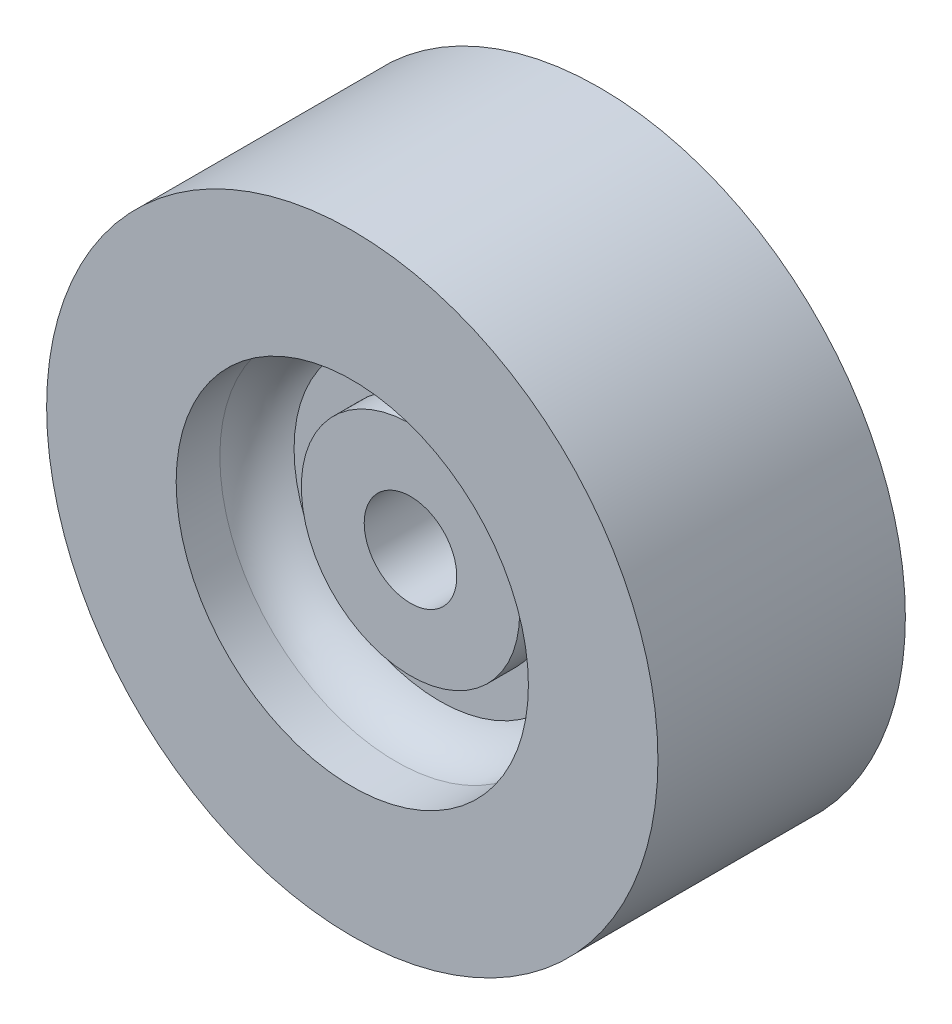
SolidWorks part; units mm, degrees
ref_plane "Front Plane" through (0, 0, 0) normal (0, 0, 1) x (1, 0, 0)
ref_plane "Top Plane" through (0, 0, 0) normal (0, 1, 0) x (1, 0, 0)
ref_plane "Right Plane" through (0, 0, 0) normal (1, 0, 0) x (0, 0, -1)
sketch "Sketch1" plane through (0, 0, 0) normal (1, 0, 0) x (0, 0, -1)
  line L0 (-0.0107, 12.1) -> (-0.0107, 14.8643)
  line L1 (-0.0107, 25.1) -> (24.9893, 25.1)
  line L2 (-0.0107, 22.1) -> (2.9893, 22.1)
  line L3 (2.9893, 10) -> (2.9893, 7.5)
  line L4 (2.9893, 7.5) -> (0.9893, 7.5)
  line L5 (0.9893, 7.5) -> (0.9893, 0)
  line L6 (-13.2759, 0) -> (14.215, 0) construction
  line L7 (-0.0107, 22.1) -> (-0.0107, 25.1)
  line L8 (24.9893, 25.1) -> (24.9893, 22.1)
  line L9 (24.9893, 22.1) -> (4.0868, 22.1)
  line L10 (0.9893, 14.8643) -> (0.9893, 12.992)
  line L11 (4.0868, 10) -> (8.0868, 10)
  line L12 (8.0868, 10) -> (8.0868, 0)
  line L13 (8.0868, 0) -> (0.9893, 0)
  arc A0 (-0.0107, 12.1) -> (2.9893, 10) centre (-0.3983, 8.3534) cw
  arc A1 (4.0868, 22.1) -> (0.9893, 14.8643) centre (9.2266, 15.6189) ccw
  arc A2 (0.9893, 12.992) -> (4.0868, 10) centre (-0.1123, 8.7522) cw
  spline S0 degree 3 poles (2.9893, 22.1) (1.2339, 21.0874) (0.2751, 20.019) (-0.0107, 14.8643) knots 0 0 0 0 1 1 1 1
  point P6 (3, 12)
  dimension "D5" = 2.2559
  dimension "D2" = 25
  dimension "D3" = 3
  dimension "D4" = 3
  dimension "D6" = 2
  dimension "D7" = 2.5
  dimension "D8" = 2
  dimension "D9" = 13
  dimension "D10" = 1
  dimension "D11" = 1
  dimension "D12" = 4
revolve "Revolve1" add sketch "Sketch1" angle 360 about L6
sketch "Sketch2" plane through (0, 0, 0.0107) normal (0, 0, 1) x (1, 0, 0)
  line L0 (0, 22.1) -> (0, 0) construction
  line L1 (-10, 19.7081) -> (-2.1298, 16.0027)
  line L2 (2.1298, 16.0027) -> (10, 19.7081)
  line L3 (15.6534, 15.6007) -> (14.5614, 6.9707)
  line L4 (15.8777, 2.9195) -> (21.8337, -3.4204)
  line L5 (19.6743, -10.0664) -> (11.1292, -11.6946)
  line L6 (7.6831, -14.1984) -> (3.494, -21.8221)
  line L7 (-3.494, -21.8221) -> (-7.6831, -14.1984)
  line L8 (-11.1292, -11.6946) -> (-19.6743, -10.0664)
  line L9 (-21.8337, -3.4204) -> (-15.8777, 2.9195)
  line L10 (-14.5614, 6.9707) -> (-15.6534, 15.6007)
  circle A0 centre (0, 0) radius 22.1 construction
  circle A1 centre (0, 0) radius 22.1 construction
  arc A2 (-2.1298, 16.0027) -> (2.1298, 16.0027) centre (0, 20.5264) ccw
  arc A3 (10, 19.7081) -> (-10, 19.7081) centre (0, 0) ccw
  arc A4 (14.5614, 6.9707) -> (15.8777, 2.9195) centre (19.5218, 6.343) ccw
  arc A5 (21.8337, -3.4204) -> (15.6534, 15.6007) centre (0, 0) ccw
  arc A6 (11.1292, -11.6946) -> (7.6831, -14.1984) centre (12.0651, -16.6062) ccw
  arc A7 (3.494, -21.8221) -> (19.6743, -10.0664) centre (0, 0) ccw
  arc A8 (-7.6831, -14.1984) -> (-11.1292, -11.6946) centre (-12.0651, -16.6062) ccw
  arc A9 (-19.6743, -10.0664) -> (-3.494, -21.8221) centre (0, 0) ccw
  arc A10 (-15.8777, 2.9195) -> (-14.5614, 6.9707) centre (-19.5218, 6.343) ccw
  arc A11 (-15.6534, 15.6007) -> (-21.8337, -3.4204) centre (0, 0) ccw
  point P12 (0, 15)
  point P35 (0, 0)
  dimension "D3" = 5
  dimension "D1" = 10
  dimension "D2" = 15
  dimension "D4" = 5
extrude "Cut-Extrude1" cut sketch "Sketch2" against normal blind 10
sketch "Sketch3" plane through (0, 0, -8.0868) normal (0, 0, -1) x (-1, 0, 0)
  circle A0 centre (0, 0) radius 6
  dimension "D1" = 12
extrude "Boss-Extrude1" add sketch "Sketch3" along normal blind 25
sketch "Sketch4" plane through (0, 0, -33.0868) normal (0, 0, -1) x (-1, 0, 0)
  line L0 (-2.5475, 2.4) -> (2.5475, 2.4)
  line L1 (-3.5, 0) -> (3.5, 0) construction
  line L2 (-2.5475, -2.4) -> (2.5475, -2.4)
  arc A0 (-2.5475, 2.4) -> (-2.5475, -2.4) centre (0, 0) ccw
  arc A1 (2.5475, -2.4) -> (2.5475, 2.4) centre (0, 0) ccw
  dimension "D1" = 7
  dimension "D2" = 2.4
extrude "Cut-Extrude2" cut sketch "Sketch4" against normal blind 12
sketch "Sketch5" plane through (0, 0, 0) normal (1, 0, 0) x (0, 0, -1)
  line L1 (-0.0107, 25.1) -> (-0.0107, -25.1) construction
  line L2 (24.9893, -25.1) -> (24.9893, 25.1) construction
  line L3 (12.4893, 21.6) -> (12.4893, 27) construction
  line L4 (0, 0) -> (33.0868, 0) construction
  line L5 (33.0868, -2.4) -> (33.0868, 2.4) construction
  line L6 (-0.0107, 14.6) -> (-0.0107, 24.9185)
  line L7 (-0.0107, 24.9185) -> (24.9893, 25.1)
  line L8 (24.9893, 25.1) -> (24.9893, 14.6)
  arc A0 (12.4893, 21.6) -> (0.6779, 20.7166) centre (11.5988, -45.8941) ccw
  arc A1 (-0.1468, 19.8936) -> (-0.0107, 14.6) centre (13.6641, 17.6) ccw
  arc A2 (-0.1468, 19.8936) -> (0.6779, 20.7166) centre (0.8397, 19.7297) cw
  arc A3 (25.1253, 19.8936) -> (24.9893, 14.6) centre (11.3145, 17.6) cw
  arc A4 (25.1253, 19.8936) -> (24.3006, 20.7166) centre (24.1389, 19.7297) ccw
  arc A5 (12.4893, 21.6) -> (24.3006, 20.7166) centre (13.3798, -45.8941) cw
  point P6 (12.4893, 21.6)
  point P7 (-0.0107, 20.6)
  point P8 (12.4893, 31.1)
  point P21 (-0.0107, 20.6)
  dimension "D3" = 67.5
  dimension "D4" = 14
  dimension "D5" = 1
  dimension "D2" = 6
  dimension "D6" = 21.6
revolve "Revolve2" add sketch "Sketch5" angle 360 about L4 rebuild error yes other way angle 360
sketch "Croquis2" plane through (0, 0, -24.9893) normal (0, 0, -1) x (-1, 0, 0)
  circle A0 centre (0, 0) radius 22.1
  circle A1 centre (0, 0) radius 25.1
extrude "Cortar-Extruir2" cut sketch "Croquis2" against normal blind 10
sketch "Croquis3" plane through (0, 0, -33.0868) normal (0, 0, -1) x (-1, 0, 0)
  circle A1 centre (0, 0) radius 6
  circle A2 centre (0, 0) radius 6
  dimension "D1" = 0
extrude "Cortar-Extruir3" cut sketch "Croquis3" against normal blind 26
sketch "Croquis5" plane through (0, 0, -8.0868) normal (0, 0, -1) x (-1, 0, 0)
  circle A1 centre (0, 0) radius 10
  circle A2 centre (0, 0) radius 10
  dimension "D1" = 0
extrude "Cortar-Extruir4" cut sketch "Croquis5" against normal up to surface (1 mm away) up to face at (-6, 0, -7.0868)
sketch "Croquis6" plane through (0, 0, -7.0868) normal (0, 0, -1) x (-1, 0, 0)
  circle A0 centre (0, 0) radius 3.1817
extrude "Cortar-Extruir5" cut sketch "Croquis6" against normal blind 26
sketch "Croquis7" plane through (0, 0, 0.0107) normal (0, 0, 1) x (1, 0, 0)
  circle A0 centre (0, 0) radius 20
  circle A1 centre (0, 0) radius 25.1
  dimension "D1" = 40
extrude "Cortar-Extruir6" cut sketch "Croquis7" against normal blind 100
sketch "Croquis8" plane through (0, 0, 0.0107) normal (0, 0, 1) x (1, 0, 0)
  circle A0 centre (0, 0) radius 21
  circle A1 centre (0, 0) radius 14
  dimension "D1" = 28
  dimension "42" = 42
extrude "Saliente-Extruir1" add sketch "Croquis8" against normal blind 14
sketch "Croquis9" plane through (0, 0, 0.0107) normal (0, 0, 1) x (1, 0, 0)
  circle A0 centre (0, 0) radius 12.1
  circle A1 centre (0, 0) radius 21
  circle A2 centre (0, 0) radius 21
  dimension "D1" = 0
extrude "Saliente-Extruir2" add sketch "Croquis9" along normal blind 3
